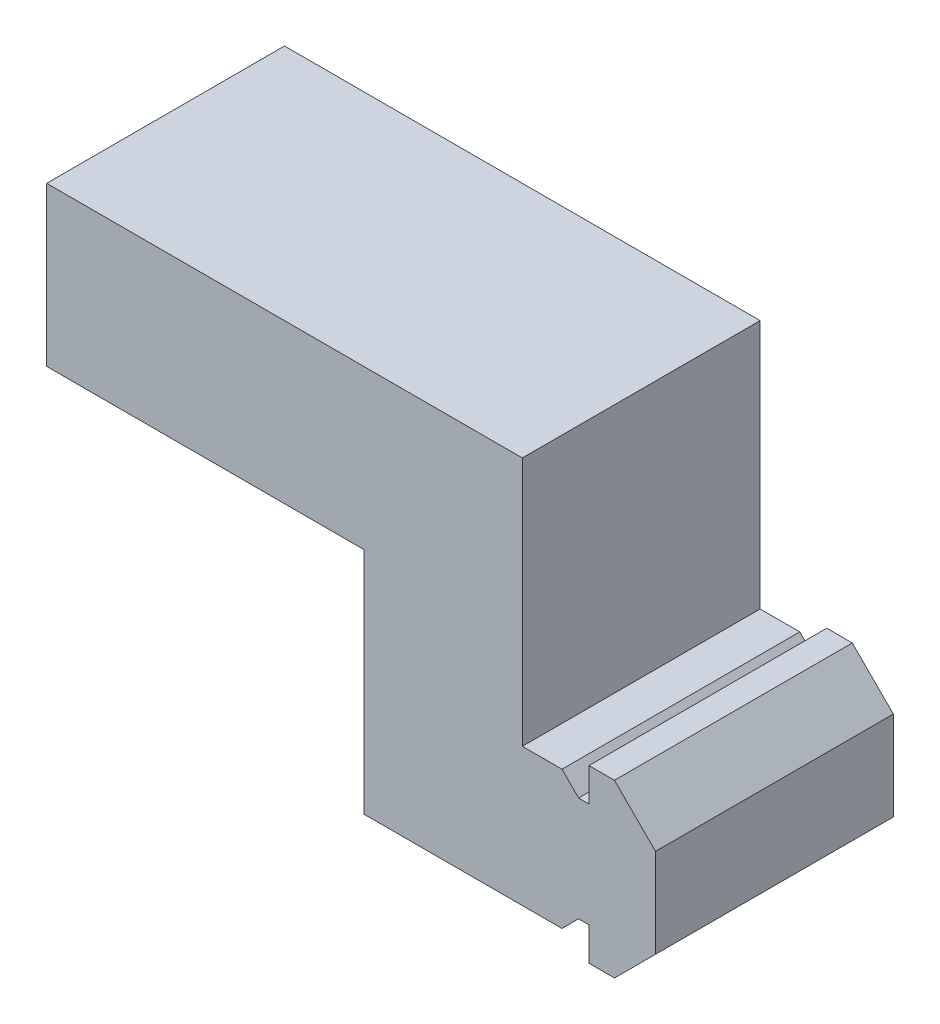
SolidWorks part; units mm, degrees
ref_plane "Front Plane" through (0, 0, 0) normal (0, 0, 1) x (1, 0, 0)
ref_plane "Top Plane" through (0, 0, 0) normal (0, 1, 0) x (1, 0, 0)
ref_plane "Right Plane" through (0, 0, 0) normal (1, 0, 0) x (0, 0, -1)
sketch "Sketch1" plane through (0, 0, 0) normal (0, 0, 1) x (1, 0, 0)
  line L0 (-3.6658, 8.0945) -> (-2.6158, 7.0445)
  line L1 (-1.9658, 7.0445) -> (-2.6158, 7.0445)
  line L2 (-1.9658, 7.0445) -> (-1.9658, 9.1445)
  line L3 (-1.9658, 9.1445) -> (-0.3547, 9.1445)
  line L4 (2.2342, 6.5556) -> (-0.3547, 9.1445)
  line L5 (2.2342, 6.5556) -> (2.2342, 0.9334)
  line L6 (2.2342, 0.9334) -> (-0.3547, -1.6555)
  line L7 (-1.9658, -1.6555) -> (-0.3547, -1.6555)
  line L8 (-1.9658, -1.6555) -> (-1.9658, 0.4445)
  line L9 (-1.9658, 0.4445) -> (-2.6158, 0.4445)
  line L10 (-2.6158, 0.4445) -> (-3.6658, -0.6055)
  line L11 (-3.6658, -0.6055) -> (-3.6658, 8.0945)
  line L12 (-3.6658, 3.7445) -> (2.2342, 3.7445) construction
  line L13 (-2.6158, 7.0445) -> (-2.6158, 0.4445) construction
  point P14 (-2.2908, 7.0445)
  point P15 (-0.7158, 3.7445)
  point P16 (0, 0)
  point P17 (-3.6943, 4.8554)
  point P18 (0, 0)
  point P19 (0, 0)
  point P20 (-2.7234, 0.7758)
  point P21 (-2.7398, 7.4405)
  point P22 (0, 0)
  point P23 (-2.6544, 7.4765)
  point P24 (0, 0)
  point P25 (-2.8307, 0.8734)
  point P26 (-2.8001, 0.9088)
  point P27 (-2.8214, 7.6036)
  point P28 (-2.6243, 7.6545)
  point P29 (-1.8847, 7.3017)
  point P30 (-1.8966, 7.1395)
  point P31 (0, 0)
  line B0 (6.1907, 3.7445) -> (-3.8093, 3.7445) construction
  line B1 (2.5007, 3.7445) -> (2.2907, 3.5345)
  line B2 (2.2907, 3.5345) -> (2.2907, 0.9052)
  line B3 (2.2907, 0.9052) -> (-0.3699, -1.7555)
  line B4 (-0.3699, -1.7555) -> (-2.0093, -1.7555)
  line B5 (-2.0093, -1.7555) -> (-2.0093, 0.3495)
  line B6 (-2.0093, 0.3495) -> (-2.6243, 0.3495)
  line B7 (-2.6243, 0.3495) -> (-3.8093, -0.8355)
  line B8 (-3.8093, -0.8355) -> (-3.8093, 8.3245)
  line B9 (6.1907, 3.7445) -> (0.2776, -2.1687) construction
  line B10 (-2.6243, 7.1395) -> (-3.8093, 8.3245)
  line B11 (-2.0093, 7.1395) -> (-2.6243, 7.1395)
  line B12 (-2.0093, 9.2445) -> (-2.0093, 7.1395)
  line B13 (-0.3699, 9.2445) -> (-2.0093, 9.2445)
  line B14 (2.2907, 6.5838) -> (-0.3699, 9.2445)
  line B15 (2.2907, 3.9545) -> (2.2907, 6.5838)
  line B16 (2.5007, 3.7445) -> (2.2907, 3.9545)
  dimension "D1" = 45
  dimension "D2" = 45
  dimension "D3" = 10.8
  dimension "D4" = 4.2
  dimension "D5" = 6.6
  dimension "D6" = 1.7
  dimension "D7" = 135
  dimension "D8" = 8.7
sketch_block_instance "V Slot 2-7"
sketch_block "V Slot 2" parameters "D1"=10, "D2"=11, "D3"=4.3, "D4"=1.8, "D5"=0.21, "D6"=45, "D7"=9.16, "D8"=1.5, "D9"=6.79, "D10"=3.7627
extrude "Boss-Extrude1" add sketch "Sketch1" along normal blind 15 contours L11 L10 L9 L8 L7 L6 L5 L4 L3 L2 L1 L0 region at (-0.7523, 3.7445, 0)
sketch "Sketch2" plane through (-3.6658, 0, 0) normal (-1, 0, 0) x (0, 0, 1)
  line L0 (15, 8.0945) -> (0, 8.0945) construction
  line L1 (0, 8.0945) -> (15, 8.0945)
  line L2 (0, 8.0945) -> (0, -0.6055)
  line L3 (0, -0.6055) -> (15, -0.6055)
  line L4 (15, 8.0945) -> (15, -0.6055)
  line L7 (0, -0.6055) -> (0, 8.0945) construction
  point P4 (10, 8.8884)
  point P8 (10, 8.8884)
  point P9 (0, 0)
  point P12 (0, 3.7445)
  point P13 (0, 0)
  point P14 (10, 0.81)
extrude "Boss-Extrude2" add sketch "Sketch2" along normal blind 12.5
sketch "Sketch3" plane through (0, 8.0945, 0) normal (0, 1, 0) x (1, 0, 0)
  line L0 (-16.1658, 0) -> (-3.6658, 0) construction
  line L1 (-16.1658, -15) -> (-6.1658, -15)
  line L2 (-16.1658, -15) -> (-16.1658, 0)
  line L3 (-16.1658, 0) -> (-6.1658, 0)
  line L4 (-6.1658, -15) -> (-6.1658, 0)
  dimension "D1" = 10
extrude "Boss-Extrude3" add sketch "Sketch3" along normal blind 15.75
sketch "Sketch5" plane through (-16.1658, 0, 0) normal (-1, 0, 0) x (0, 0, 1)
  line L0 (15, -0.6055) -> (15, 23.8445) construction
  line L1 (0, 23.8445) -> (15, 23.8445)
  line L2 (0, 23.8445) -> (0, 13.8445)
  line L3 (0, 13.8445) -> (15, 13.8445)
  line L4 (15, 23.8445) -> (15, 13.8445)
  dimension "D1" = 10
extrude "Boss-Extrude4" add sketch "Sketch5" along normal blind 20
